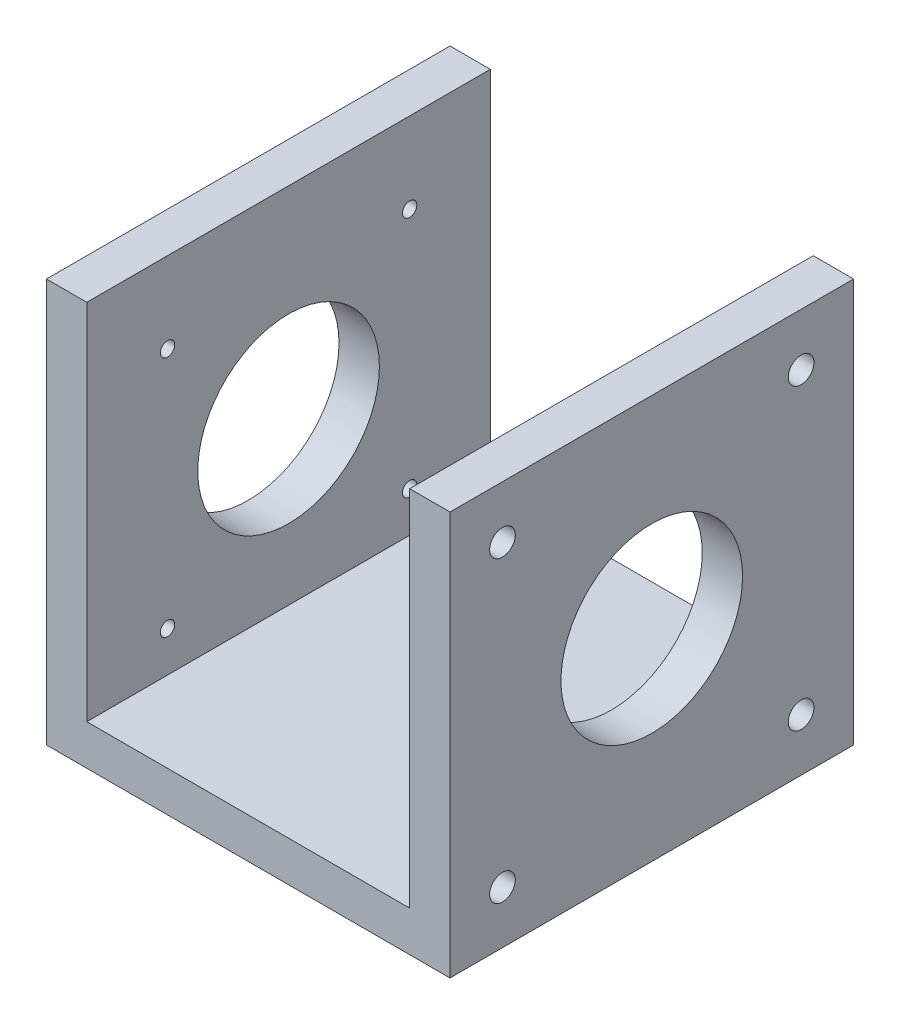
SolidWorks part; units mm, degrees
material "6061 Alloy"
ref_plane "Front Plane" through (0, 0, 0) normal (0, 0, 1) x (1, 0, 0)
ref_plane "Top Plane" through (0, 0, 0) normal (0, 1, 0) x (1, 0, 0)
ref_plane "Right Plane" through (0, 0, 0) normal (1, 0, 0) x (0, 0, -1)
sketch "Sketch1" plane through (0, 0, 0) normal (0, 1, 0) x (1, 0, 0)
  line L1 (-31.75, -31.75) -> (31.75, -31.75)
  line L2 (-31.75, -31.75) -> (-31.75, 31.75)
  line L3 (-31.75, 31.75) -> (31.75, 31.75)
  line L4 (31.75, -31.75) -> (31.75, 31.75)
  line L5 (-31.75, -31.75) -> (31.75, 31.75) construction
  line L6 (-31.75, 31.75) -> (31.75, -31.75) construction
  line L7 (-31.75, 31.75) -> (-25.4, 31.75)
  line L8 (-31.75, 31.75) -> (-31.75, -31.75)
  line L9 (-31.75, -31.75) -> (-25.4, -31.75)
  line L10 (-25.4, 31.75) -> (-25.4, -31.75)
  line L11 (31.75, 31.75) -> (25.4, 31.75)
  line L12 (31.75, 31.75) -> (31.75, -31.75)
  line L13 (31.75, -31.75) -> (25.4, -31.75)
  line L14 (25.4, 31.75) -> (25.4, -31.75)
  point P0 (0, 0)
  dimension "D1" = 63.5
  dimension "D2" = 63.5
  dimension "D3" = 6.35
  dimension "D4" = 6.35
extrude "Boss-Extrude1" add sketch "Sketch1<3>" along normal blind 63.5 separate body contours L3 L14 L1 L4 region at (28.575, 0, 0)
sketch "Sketch1<3>" plane through (0, 0, 0) normal (0, 1, 0) x (1, 0, 0) same geometry as "Sketch1"
extrude "Boss-Extrude2" add sketch "Sketch1" along normal blind 6.35 contours L14 L3 L10 L1 region at (0, 0, 0)
extrude "Boss-Extrude3" add sketch "Sketch1<6>" along normal blind 63.5 contours L10 L3 L2 L1 region at (-28.575, 0, 0)
sketch "Sketch1<6>" plane through (0, 0, 0) normal (0, 1, 0) x (1, 0, 0) same geometry as "Sketch1"
sketch "Sketch2" plane through (31.75, 0, 0) normal (1, 0, 0) x (0, 0, -1)
  line L0 (-31.75, 63.5) -> (31.75, 63.5) construction
  line L1 (-31.75, 63.5) -> (-31.75, 0) construction
  circle A0 centre (0, 31.75) radius 14.2875
  dimension "D1" = 28.575
  dimension "D2" = 31.75
  dimension "D3" = 31.75
extrude "Cut-Extrude1" cut sketch "Sketch2" against normal through all
hole_wizard "#43 (0.089) Diameter Hole1" positions "Sketch4" profile "Sketch3" hole size "#43" standard "ANSI Inch"
sketch "Sketch4" plane through (-31.75, 0, 0) normal (-1, 0, 0) x (0, 0, 1)
  line L0 (31.75, 0) -> (-31.75, 0) construction
  line L1 (-31.75, 63.5) -> (-31.75, 0) construction
  line L2 (31.75, 63.5) -> (31.75, 0) construction
  line L3 (31.75, 63.5) -> (-31.75, 63.5) construction
  point P0 (-19.05, 50.8)
  point P2 (19.05, 50.8)
  point P4 (19.05, 12.7)
  point P6 (-19.05, 12.7)
  dimension "D1" = 12.7
  dimension "D2" = 12.7
  dimension "D3" = 12.7
  dimension "D4" = 12.7
  dimension "D5" = 12.7
  dimension "D6" = 12.7
  dimension "D7" = 12.7
  dimension "D8" = 12.7
sketch "Sketch3" plane through (-31.75, 50.8, -19.05) normal (0, 1, 0) x (0, 0, 1)
  line L0 (0, 0) -> (0, 26.0792)
  line L1 (0, 26.0792) -> (1.1303, 25.4)
  line L2 (1.1303, 25.4) -> (1.1303, 0)
  line L5 (1.1303, 0) -> (0, 0)
  line L10 (0, 26.0792) -> (-1.1303, 25.4) construction
  line L11 (0, -6.35) -> (0, 107.95) construction
  dimension "Hole Dia." = 2.2606
  dimension "Hole Depth" = 25.4
  dimension "Drill Angle" = 118
hole_wizard "#10-32 Tapped Hole1" positions "Sketch6" profile "Sketch7" tap size "#10-32" standard "ANSI Inch" end condition up to next
sketch "Sketch6" plane through (31.75, 0, 0) normal (1, 0, 0) x (0, 0, -1)
  line L0 (31.75, 63.5) -> (31.75, 0) construction
  line L1 (-31.75, 0) -> (31.75, 0) construction
  line L2 (-31.75, 63.5) -> (-31.75, 0) construction
  point P0 (-23.495, 55.245)
  point P2 (23.495, 55.245)
  point P4 (23.495, 8.255)
  point P6 (-23.495, 8.255)
  dimension "D1" = 46.99
  dimension "D2" = 46.99
  dimension "D3" = 46.99
  dimension "D4" = 46.99
  dimension "D5" = 8.255
  dimension "D6" = 8.255
  dimension "D7" = 8.255
  dimension "D8" = 8.255
sketch "Sketch7" plane through (31.75, 55.245, 23.495) normal (0, 1, 0) x (0, 0, -1)
  line L0 (0, 0) -> (0, 6.35)
  line L1 (0, 6.35) -> (2.0193, 6.35)
  line L2 (2.0193, 6.35) -> (2.0193, 0)
  line L5 (2.0193, 0) -> (0, 0)
  line L11 (0, -6.35) -> (0, 107.95) construction
  dimension "Thread Major Dia." = 4.0386
  dimension "Thru Tap Drill Depth" = 6.35
